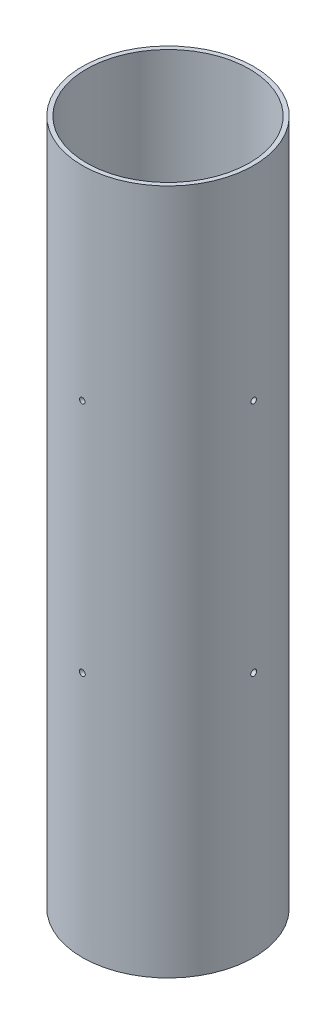
SolidWorks part; units mm, degrees
material "E-Glass Fiber"
ref_plane "Front Plane" through (0, 0, 0) normal (0, 0, 1) x (1, 0, 0)
ref_plane "Top Plane" through (0, 0, 0) normal (0, 1, 0) x (1, 0, 0)
ref_plane "Right Plane" through (0, 0, 0) normal (1, 0, 0) x (0, 0, -1)
sketch "Sketch1" plane through (0, 0, 0) normal (0, 1, 0) x (1, 0, 0)
  circle A0 centre (0, 0) radius 50.8
  dimension "D1" = 101.6
extrude "Coupler Extrusion" add sketch "Sketch1" along normal blind 406.4 thin thin type one direction reverse wall 2.54
ref_plane "Plane1" through (0, 0, 50.8) normal (0, 0, 1) x (1, 0, 0)
sketch "Sketch2" plane through (0, 0, 50.8) normal (0, 0, 1) x (1, 0, 0)
  line L0 (0, 406.4) -> (0, 0) construction
  line L1 (48.26, 406.4) -> (-48.26, 406.4) construction
  circle A0 centre (0, 285.75) radius 1.6383
  dimension "D1" = 3.2766
  dimension "D2" = 120.65
extrude "Bulkhead Hole" cut sketch "Sketch2" against normal up to next
pattern_circular "CirPattern1" count 4 over 360 about axis through (0, 406.4, 0) along (0, -1, 0) of "Bulkhead Hole"
sketch "Sketch3" plane through (0, 0, 50.8) normal (0, 0, 1) x (1, 0, 0)
  line L0 (0, 406.4) -> (0, 0) construction
  line L1 (50.8, 406.4) -> (-50.8, 406.4) construction
  line L2 (-48.26, 0) -> (48.26, 0) construction
  line L3 (-50.8, 0) -> (50.8, 0) construction
  line L4 (48.26, 406.4) -> (-48.26, 406.4) construction
  circle A0 centre (0, 146.05) radius 1.7526
  dimension "D1" = 3.5052
  dimension "D2" = 146.05
  dimension "D3" = 260.35
extrude "Cut-Extrude1" cut sketch "Sketch3" against normal up to next
pattern_circular "CirPattern2" count 4 over 360 about axis through (0, 406.4, 0) along (0, -1, 0) of "Cut-Extrude1" reverse direction yes
